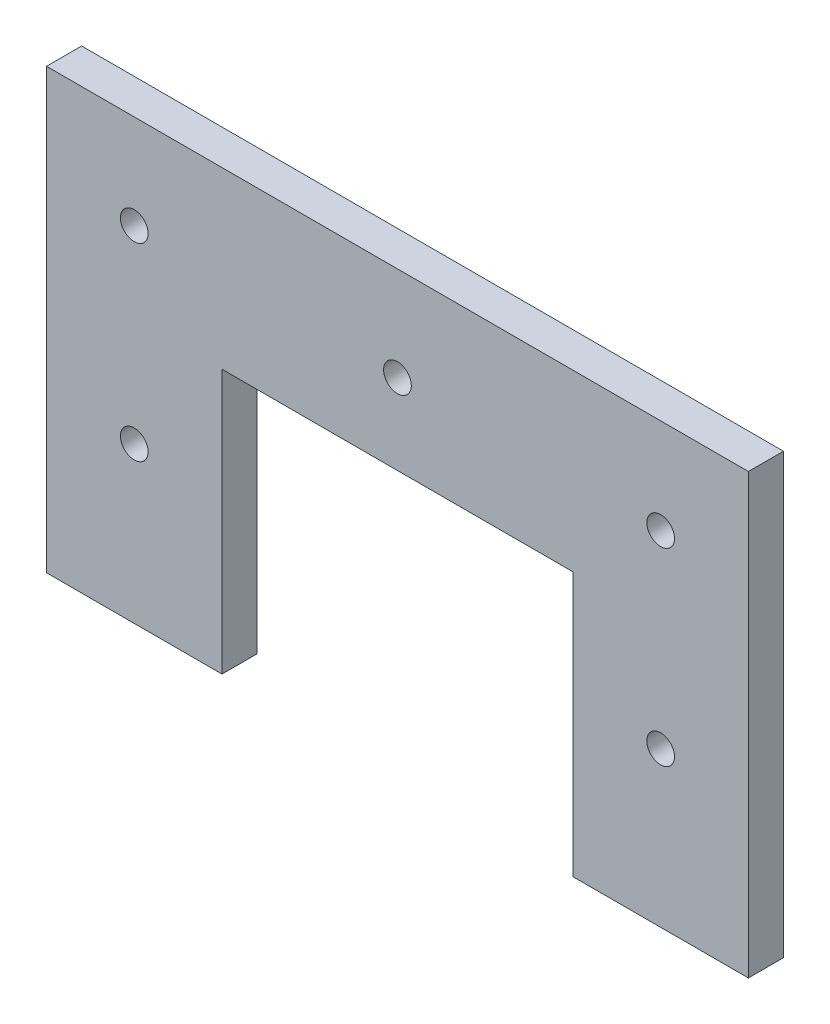
SolidWorks part; units mm, degrees
ref_plane "Alzado" through (0, 0, 0) normal (0, 0, 1) x (1, 0, 0)
ref_plane "Planta" through (0, 0, 0) normal (0, 1, 0) x (1, 0, 0)
ref_plane "Vista lateral" through (0, 0, 0) normal (1, 0, 0) x (0, 0, -1)
sketch "Croquis1" plane through (0, 0, 0) normal (0, 0, 1) x (1, 0, 0)
  line L1 (20.1881, 6.6994) -> (60.1881, 6.6994)
  line L2 (0.1881, 6.6044) -> (0.1881, 26.6044)
  line L3 (0.1881, 26.6044) -> (80.1881, 26.6044)
  line L4 (80.1881, 6.6044) -> (80.1881, 26.6044)
  line L6 (0.1881, 6.6044) -> (0.1881, -23.3956)
  line L7 (0.1881, -23.3956) -> (20.1881, -23.3956)
  line L8 (20.1881, 6.6994) -> (20.1881, -23.3956)
  line L10 (80.1881, 6.6044) -> (80.1881, -23.3956)
  line L11 (80.1881, -23.3956) -> (60.1881, -23.3956)
  line L12 (60.1881, 6.6994) -> (60.1881, -23.3956)
  circle A0 centre (40.1881, 15.8665) radius 1.58
  circle A1 centre (10.1881, 15.8665) radius 1.58
  circle A2 centre (70.1881, 15.7714) radius 1.58
  circle A3 centre (10.1881, -5.6765) radius 1.58
  circle A4 centre (70.1881, -5.7716) radius 1.58
  dimension "D7" = 3.16
  dimension "D8" = 3.16
  dimension "D9" = 3.16
  dimension "D10" = 3.16
  dimension "D11" = 3.16
  dimension "D14" = 10
  dimension "D1" = 20
  dimension "D2" = 80
  dimension "D3" = 30
  dimension "D4" = 20
  dimension "D5" = 30
  dimension "D6" = 20
  dimension "D12" = 20
  dimension "D13" = 40
  dimension "D15" = 10
  dimension "D16" = 10
  dimension "D17" = 10
  dimension "D18" = 40
extrude "Saliente-Extruir1" add sketch "Croquis1" along normal blind 4
